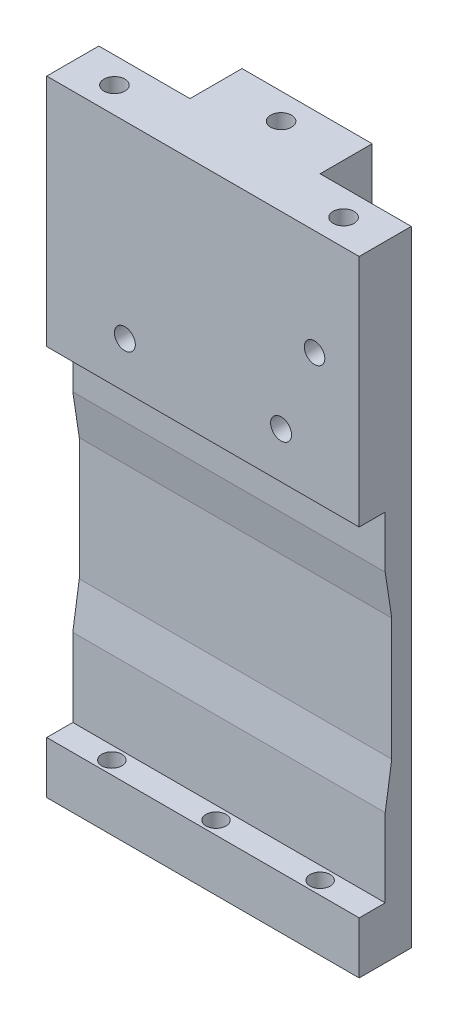
SolidWorks part; units mm, degrees
material "6061 Alloy"
ref_plane "Front Plane" through (0, 0, 0) normal (0, 0, 1) x (1, 0, 0)
ref_plane "Top Plane" through (0, 0, 0) normal (0, 1, 0) x (1, 0, 0)
ref_plane "Right Plane" through (0, 0, 0) normal (1, 0, 0) x (0, 0, -1)
sketch "Sketch1" plane through (0, 0, 0) normal (0, 1, 0) x (1, 0, 0)
  line L0 (-15.875, 6.35) -> (-15.875, 19.05)
  line L1 (38.1, -6.35) -> (-38.1, -6.35)
  line L2 (38.1, -6.35) -> (38.1, 6.35)
  line L3 (38.1, 6.35) -> (15.875, 6.35)
  line L4 (-38.1, -6.35) -> (-38.1, 6.35)
  line L5 (38.1, -6.35) -> (-38.1, 6.35) construction
  line L6 (38.1, 6.35) -> (-38.1, -6.35) construction
  line L7 (-15.875, 19.05) -> (15.875, 19.05)
  line L8 (15.875, 19.05) -> (15.875, 6.35)
  line L9 (-15.875, 6.35) -> (-38.1, 6.35)
  line L10 (0, 19.05) -> (0, 0) construction
  point P0 (0, 0)
  dimension "D1" = 76.2
  dimension "D2" = 12.7
  dimension "D3" = 31.75
  dimension "D4" = 12.7
extrude "Boss-Extrude1" add sketch "Sketch1" along normal mid plane 152.4
ref_plane "Plane1" through (0, 0, 0) normal (0, 1, 0) x (1, 0, 0)
sketch "Sketch5" plane through (0, 0, 0) normal (0, 1, 0) x (1, 0, 0)
  line L0 (-4.7625, 19.05) -> (-4.7625, 12.7)
  line L1 (15.875, 19.05) -> (-15.875, 19.05) construction
  line L2 (4.7625, 12.7) -> (4.7625, 19.05)
  line L3 (0, 0) -> (0, 12.7) construction
  line L4 (-4.7625, 19.05) -> (4.7625, 19.05)
  arc A0 (-4.7625, 12.7) -> (4.7625, 12.7) centre (0, 12.7) ccw
  point P10 (0, 7.9375)
  dimension "D1" = 11.1125
  dimension "D2" = 9.525
extrude "Cut-Extrude3" cut sketch "Sketch5" against normal mid plane 95.25
sketch "Sketch9" plane through (0, 0, 0) normal (1, 0, 0) x (0, 0, -1)
  line L0 (19.05, -52.3875) -> (12.7, -52.3875)
  line L1 (19.05, -52.3875) -> (19.05, -47.625)
  line L2 (19.05, -47.625) -> (7.9375, -47.625) construction
  line L3 (12.7, -52.3875) -> (12.7, -47.625) construction
  line L4 (7.9375, -47.625) -> (19.05, -47.625)
  arc A0 (12.7, -52.3875) -> (7.9375, -47.625) centre (12.7, -47.625) cw
  dimension "D2" = 90
  dimension "D1" = 4.7625
  dimension "D3" = 11.1125
revolve "Cut-Revolve1" cut sketch "Sketch9" angle 360 about L4
mirror "Mirror1" about plane through (0, 0, 0) normal (0, 1, 0) of "Cut-Revolve1"
ref_plane "Parting Plane" through (0, 0, 0) normal (0, 0, 1) x (1, 0, 0)
sketch "Sketch12" plane through (38.1, 0, 0) normal (1, 0, 0) x (0, 0, -1)
  line L0 (-6.35, -63.5) -> (0, -63.5)
  line L1 (-6.35, 76.2) -> (-6.35, -76.2) construction
  line L2 (0, 45.4834) -> (0, -45.4834) construction
  line L3 (0, -63.5) -> (0, -44.45)
  line L4 (0, -44.45) -> (1.5875, -33.9561)
  line L5 (1.5875, -33.9561) -> (1.5875, -4.1439)
  line L6 (1.5875, -4.1439) -> (0, 6.35)
  line L7 (0, 6.35) -> (0, 19.05)
  line L8 (0, 19.05) -> (-6.35, 19.05)
  line L9 (-6.35, 19.05) -> (-6.35, -63.5)
  line L10 (-6.35, -76.2) -> (6.35, -76.2) construction
  point P8 (1.5875, -32.0669)
  point P14 (1.5875, 14.385)
  point P15 (1.5875, -33.9561)
  dimension "D1" = 19.05
  dimension "D2" = 12.7
  dimension "D3" = 82.55
  dimension "D4" = 1.5875
  dimension "D5" = 12.7
extrude "Cut-Extrude4" cut sketch "Sketch12" against normal through all
hole_wizard "#10 (0.1935) Diameter Hole1" positions "Sketch15" profile "Sketch16" hole size "#10" standard "ANSI Inch"
sketch "Sketch15" plane through (0, -76.2, 0) normal (0, -1, 0) x (-1, 0, 0)
  line L0 (38.1, 6.35) -> (38.1, -6.35) construction
  line L1 (-38.1, -6.35) -> (-38.1, 6.35) construction
  line L3 (25.4, -3.175) -> (-25.4, -3.175) construction
  line L4 (38.1, -6.35) -> (-38.1, -6.35) construction
  point P0 (25.4, -3.175)
  point P2 (-25.4, -3.175)
  point P16 (0, -3.175)
  dimension "D1" = 12.7
  dimension "D2" = 12.7
  dimension "D3" = 3.175
sketch "Sketch16" plane through (-25.4, -76.2, 3.175) normal (1, 0, 0) x (0, 0, -1)
  line L0 (0, 0) -> (0, 20.5266)
  line L1 (0, 20.5266) -> (2.4574, 19.05)
  line L2 (2.4574, 19.05) -> (2.4574, 0)
  line L5 (2.4574, 0) -> (0, 0)
  line L10 (0, 20.5266) -> (-2.4575, 19.05) construction
  line L11 (0, -6.35) -> (0, 107.95) construction
  dimension "Hole Dia." = 4.9149
  dimension "Hole Depth" = 19.05
  dimension "Drill Angle" = 118
hole_wizard "1/4-20 Tapped Hole1" positions "Sketch17" profile "Sketch18" tap size "1/4-20" standard "ANSI Inch" end condition through all
sketch "Sketch17" plane through (0, 76.2, 0) normal (0, 1, 0) x (1, 0, 0)
  line L0 (15.875, 19.05) -> (-15.875, 19.05) construction
  line L1 (15.875, 6.35) -> (15.875, 19.05) construction
  point P0 (0, 12.7)
  dimension "D1" = 6.35
  dimension "D2" = 15.875
sketch "Sketch18" plane through (0, 76.2, -12.7) normal (1, 0, 0) x (0, 0, 1)
  line L0 (0, 0) -> (0, 152.4)
  line L1 (0, 152.4) -> (2.5527, 152.4)
  line L2 (2.5527, 152.4) -> (2.5527, 0)
  line L5 (2.5527, 0) -> (0, 0)
  line L11 (0, -6.35) -> (0, 107.95) construction
  dimension "Thru Tap Drill Dia." = 5.1054
  dimension "Thru Tap Drill Depth" = 152.4
cosmetic thread "Hole Thread1" parameters "D2"=6.35
sketch "Sketch19" plane through (0, 0, -6.35) normal (0, 0, -1) x (-1, 0, 0)
  circle A0 centre (-27.209, 50.4369) radius 2.5
  dimension "D1" = 5
extrude "Cut-Extrude5" cut sketch "Sketch19" against normal through all
hole_wizard "1/4-20 Tapped Hole2" positions "Sketch20" profile "Sketch21" tap size "1/4-20" standard "ANSI Inch"
sketch "Sketch20" plane through (0, 76.2, 0) normal (0, 1, 0) x (1, 0, 0)
  point P0 (27.94, 0)
  point P3 (-27.94, 0)
sketch "Sketch21" plane through (27.94, 76.2, 0) normal (1, 0, 0) x (0, 0, 1)
  line L0 (0, 0) -> (0, 22.225)
  line L1 (0, 22.225) -> (2.5527, 20.6912)
  line L2 (2.5527, 20.6912) -> (2.5527, 0)
  line L5 (2.5527, 0) -> (0, 0)
  line L10 (0, 22.225) -> (-2.5527, 20.6912) construction
  line L11 (0, -6.35) -> (0, 107.95) construction
  dimension "Tap Drill Dia." = 5.1054
  dimension "Tap Drill Depth" = 22.225
  dimension "Drill Angle" = 118
cosmetic thread "Hole Thread2" parameters "D1"=38.26, "D2"=6.35
cosmetic thread "Hole Thread3" parameters "D1"=38.26, "D2"=6.35
hole_wizard "1/4-20 Tapped Hole3" positions "Sketch22" profile "Sketch23" tap size "1/4-20" standard "ANSI Inch"
sketch "Sketch22" plane through (0, 0, -19.05) normal (0, 0, -1) x (-1, 0, 0)
  line L0 (9.525, 57.15) -> (-9.525, 57.15) construction
  line L2 (0, 57.15) -> (0, 0) construction
  line L4 (-15.875, -76.2) -> (15.875, -76.2) construction
  line L5 (-9.525, 57.15) -> (-9.525, -66.675) construction
  line L7 (-9.525, -66.675) -> (9.525, -66.675) construction
  point P0 (-9.525, -66.675)
  point P2 (9.525, 57.15)
  point P4 (-9.525, 57.15)
  point P26 (9.525, -66.675)
  dimension "D1" = 19.05
  dimension "D2" = 123.825
  dimension "D3" = 9.525
  dimension "D4" = 19.05
sketch "Sketch23" plane through (9.525, -66.675, -19.05) normal (1, 0, 0) x (0, 1, 0)
  line L0 (0, 0) -> (0, 10.5838)
  line L1 (0, 10.5838) -> (2.5527, 9.05)
  line L2 (2.5527, 9.05) -> (2.5527, 0)
  line L5 (2.5527, 0) -> (0, 0)
  line L10 (0, 10.5838) -> (-2.5527, 9.05) construction
  line L11 (0, -6.35) -> (0, 107.95) construction
  dimension "Tap Drill Dia." = 5.1054
  dimension "Tap Drill Depth" = 9.05
  dimension "Drill Angle" = 118
cosmetic thread "Hole Thread4" parameters "D1"=38.26, "D2"=6.35
cosmetic thread "Hole Thread5" parameters "D1"=38.26, "D2"=6.35
cosmetic thread "Hole Thread6" parameters "D1"=38.26, "D2"=6.35
cosmetic thread "Hole Thread9" parameters "D1"=38.26, "D2"=6.35
hole_wizard "1/4-20 Tapped Hole4" positions "Sketch24" profile "Sketch25" tap size "1/4-20" standard "ANSI Inch"
sketch "Sketch24" plane through (0, 0, 6.35) normal (0, 0, 1) x (1, 0, 0)
  point P0 (19.05, 30.2607)
  point P3 (-19.05, 30.2607)
  point P6 (0, 0)
  point P9 (-19.05, 30.2607)
sketch "Sketch25" plane through (19.05, 30.2607, 6.35) normal (1, 0, 0) x (0, -1, 0)
  line L0 (0, 0) -> (0, 8.89)
  line L1 (0, 8.89) -> (2.5527, 7.3562)
  line L2 (2.5527, 7.3562) -> (2.5527, 0)
  line L5 (2.5527, 0) -> (0, 0)
  line L10 (0, 8.89) -> (-2.5527, 7.3562) construction
  line L11 (0, -6.35) -> (0, 107.95) construction
  dimension "Tap Drill Dia." = 5.1054
  dimension "Tap Drill Depth" = 8.89
  dimension "Drill Angle" = 118
cosmetic thread "Hole Thread7" parameters "D1"=12.7, "D2"=6.35
cosmetic thread "Hole Thread8" parameters "D1"=12.7, "D2"=6.35
